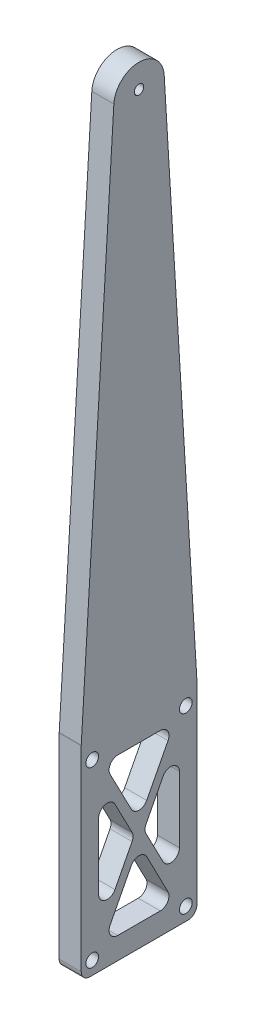
SolidWorks part; units mm, degrees
material "6061 Alloy"
ref_plane "Front Plane" through (0, 0, 0) normal (0, 0, 1) x (1, 0, 0)
ref_plane "Top Plane" through (0, 0, 0) normal (0, 1, 0) x (1, 0, 0)
ref_plane "Right Plane" through (0, 0, 0) normal (1, 0, 0) x (0, 0, -1)
sketch "Sketch1" plane through (0, 0, 0) normal (1, 0, 0) x (0, 0, -1)
  line L0 (-13.4747, 0) -> (13.4747, 0) construction
  line L1 (0, 0) -> (0, 160) construction
  line L2 (-13.4747, 0) -> (0, 160) construction
  line L3 (0, 160) -> (13.4747, 0) construction
  line L4 (13.4747, 0) -> (-13.4747, 0) construction
  line L8 (-13.4747, 0) -> (13.4747, 0) construction
  line L9 (-13.4747, 0) -> (-13.4747, -50) construction
  line L10 (13.4747, 0) -> (13.4747, -50) construction
  line L11 (-13.4747, -50) -> (13.4747, -50) construction
  line L16 (-16.645, -53.81) -> (16.645, -53.81)
  line L17 (-16.645, -53.81) -> (-16.645, 5.15)
  line L18 (16.645, -53.81) -> (16.645, 5.15)
  line L19 (-16.645, 5.15) -> (16.645, 5.15)
  line L20 (-16.645, 5.15) -> (-7.2492, 160.4386)
  line L21 (-7.2492, 160.4386) -> (7.2492, 160.4386) construction
  line L22 (7.2492, 160.4386) -> (16.645, 5.15)
  circle A0 centre (-13.4747, 0) radius 1.8288
  circle A1 centre (0, 160) radius 4.7625 construction
  circle A2 centre (13.4747, 0) radius 1.8288
  circle A3 centre (-13.4747, -50) radius 1.8288
  circle A4 centre (13.4747, -50) radius 1.8288
  arc A5 (-7.2492, 160.4386) -> (7.2492, 160.4386) centre (0, 160) cw
  point P4 (0, 0)
  point P6 (0, 0)
  point P7 (0, -53.81)
  point P21 (0, 0)
  dimension "D3" = 3.6576
  dimension "D4" = 9.525
  dimension "D9" = 2.5
  dimension "D1" = 26.9494
  dimension "D5" = 50
  dimension "D6" = 3.81
  dimension "D7" = 160
  dimension "D8" = 5.15
  dimension "D2" = 33.29
extrude "Boss-Extrude1" add sketch "Sketch1" along normal blind 6.35 contours A5 L20 L19 L22 | L19 L17 L16 L18 A4 A3 A2 A0 region at (0, -24.3153, 0) region at (0, 74.449, 0)
sketch "Sketch2" plane through (6.35, 0, 0) normal (1, 0, 0) x (0, 0, -1)
  line L3 (-11.645, -47.5) -> (-11.645, -2.5)
  line L4 (11.645, -47.5) -> (11.645, -2.5)
  line L5 (-11.645, -2.5) -> (11.645, -2.5)
  line L6 (-11.645, -47.5) -> (11.645, -47.5)
  line L7 (-11.645, -47.5) -> (11.645, -2.5) construction
  line L8 (-16.645, -53.81) -> (-16.645, 5.15) construction
  line L15 (11.645, -47.5) -> (-11.645, -2.5) construction
  line L24 (16.645, -53.81) -> (16.645, 5.15) construction
  line L31 (11.645, -44.7805) -> (-10.2375, -2.5)
  line L32 (-10.2375, -47.5) -> (11.645, -5.2195)
  line L33 (10.2375, -47.5) -> (-11.645, -5.2195)
  line L34 (-11.645, -44.7805) -> (10.2375, -2.5)
  line L35 (12.7551, -46.9254) -> (-10.5349, -1.9254) construction
  line L36 (10.5349, -48.0746) -> (-12.7551, -3.0746) construction
  line L37 (-10.5349, -48.0746) -> (12.7551, -3.0746) construction
  line L38 (-12.7551, -46.9254) -> (10.5349, -1.9254) construction
  circle A0 centre (13.4747, -50) radius 1.8288 construction
  circle A1 centre (13.4747, 0) radius 1.8288 construction
  point P0 (11.645, -25)
  point P2 (0, -47.5)
  point P28 (0, -25)
  dimension "D4" = 2.5
  dimension "D1" = 5
  dimension "D2" = 5
  dimension "D3" = 2.5
  dimension "D5" = 1.25
  dimension "D6" = 1.25
extrude "Cut-Extrude1" cut sketch "Sketch2" against normal through all contours L32 L31 L4 | L6 L33 L32 | L3 L34 L33 | L31 L34 L5 region at (6.35, -25, 8.2325) region at (6.35, -40.9065, 0) region at (6.35, -9.0935, 0) region at (6.35, -25, -8.2325)
fillet "Fillet1" radius 2.5 12 edges at (3.175, -2.5, -10.2375) (3.175, -22.2805, 0) (3.175, -2.5, 10.2375) (3.175, -5.2195, -11.645) (3.175, -44.7805, -11.645) (3.175, -25, -1.4075) (3.175, -47.5, 10.2375) (3.175, -47.5, -10.2375) (3.175, -27.7195, 0) (3.175, -25, 1.4075) (3.175, -5.2195, 11.645) (3.175, -44.7805, 11.645)
fillet "Fillet2" radius 2.5 4 edges at (3.175, 5.15, 16.645) (3.175, 5.15, -16.645) (3.175, -53.81, -16.645) (3.175, -53.81, 16.645)
hole_wizard "#6-32 Tapped Hole1" positions "Sketch3" profile "Sketch4" tap size "#6-32" standard "ANSI Inch" end condition through all
sketch "Sketch3" plane through (6.35, 0, 0) normal (1, 0, 0) x (0, 0, -1)
  line L0 (-7.2492, 160.4386) -> (7.2492, 160.4386) construction
  point P0 (0, 160.4386)
sketch "Sketch4" plane through (6.35, 160.4386, 0) normal (0, 1, 0) x (0, 0, -1)
  line L0 (0, 0) -> (0, 6.35)
  line L1 (0, 6.35) -> (1.3525, 6.35)
  line L2 (1.3525, 6.35) -> (1.3525, 0)
  line L5 (1.3525, 0) -> (0, 0)
  line L11 (0, -6.35) -> (0, 107.95) construction
  dimension "Thru Tap Drill Dia." = 2.7051
  dimension "Thru Tap Drill Depth" = 6.35
